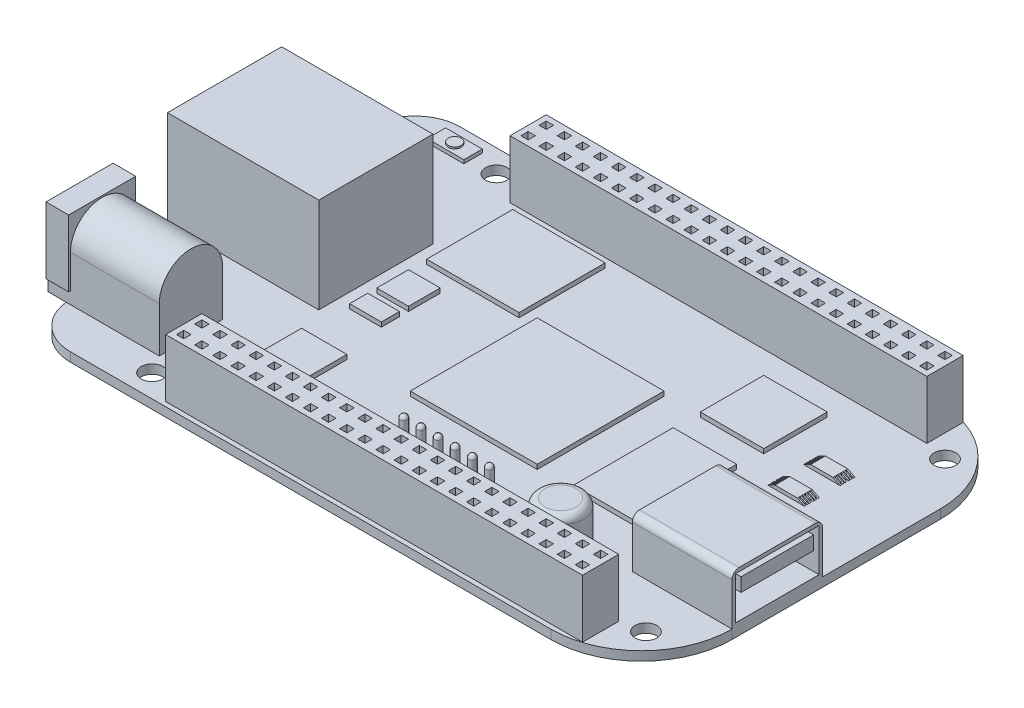
SolidWorks part; units mm, degrees
material "ABS"
ref_plane "Front Plane" through (0, 0, 0) normal (0, 0, 1) x (1, 0, 0)
ref_plane "Top Plane" through (0, 0, 0) normal (0, 1, 0) x (1, 0, 0)
ref_plane "Right Plane" through (0, 0, 0) normal (1, 0, 0) x (0, 0, -1)
sketch "Sketch1" plane through (0, 0, 0) normal (0, 1, 0) x (1, 0, 0)
  line L1 (-12.7, 0) -> (-80.01, 0)
  line L2 (0, 12.7) -> (0, 41.91)
  line L3 (-12.7, 54.61) -> (-80.01, 54.61)
  line L4 (-86.36, 6.35) -> (-86.36, 48.26)
  arc A0 (0, 12.7) -> (-12.7, 0) centre (-12.7, 12.7) cw
  arc A1 (0, 41.91) -> (-12.7, 54.61) centre (-12.7, 41.91) ccw
  arc A2 (-86.36, 6.35) -> (-80.01, 0) centre (-80.01, 6.35) ccw
  arc A3 (-86.36, 48.26) -> (-80.01, 54.61) centre (-80.01, 48.26) cw
  point P7 (0, 0)
  point P10 (0, 54.61)
  point P13 (-86.36, 0)
  dimension "D3" = 12.7
  dimension "D4" = 6.35
  dimension "D1" = 86.36
  dimension "D2" = 54.61
extrude "Boss-Extrude1" add sketch "Sketch1" along normal blind 1.27
sketch "Sketch2" plane through (0, 1.27, 0) normal (0, 1, 0) x (1, 0, 0)
  line L0 (-80.01, 0) -> (-12.7, 0) construction
  line L2 (-71.755, 51.435) -> (-71.755, 3.175) construction
  line L3 (-86.36, 48.26) -> (-86.36, 6.35) construction
  line L4 (-5.715, 48.26) -> (-5.715, 6.35) construction
  circle A0 centre (-71.755, 51.435) radius 1.524
  circle A1 centre (-71.755, 3.175) radius 1.524
  circle A2 centre (-5.715, 48.26) radius 1.524
  circle A3 centre (-5.715, 6.35) radius 1.524
  dimension "D7" = 3.048
  dimension "D1" = 48.26
  dimension "D2" = 41.91
  dimension "D3" = 6.35
  dimension "D4" = 14.605
  dimension "D5" = 80.645
  dimension "D6" = 3.175
extrude "Cut-Extrude1" cut sketch "Sketch2" along direction (0, -1, 0) on the side against the normal up to surface (1.27 mm away) up to face at (-44.4387, 0, -27.305)
sketch "Sketch3" plane through (0, 1.27, 0) normal (0, 1, 0) x (1, 0, 0)
  line L0 (-10.16, 48.895) -> (-10.16, 50.165) construction
  line L1 (-67.31, 53.975) -> (-8.89, 53.975)
  line L2 (-67.31, 53.975) -> (-67.31, 48.895)
  line L3 (-67.31, 48.895) -> (-8.89, 48.895)
  line L4 (-8.89, 53.975) -> (-8.89, 48.895)
  line L5 (-86.36, 27.305) -> (0, 27.305) construction
  line L6 (0, 12.7) -> (0, 41.91) construction
  line L7 (-66.548, 4.953) -> (-66.548, 3.937)
  line L8 (-66.548, 4.953) -> (-65.532, 4.953)
  line L9 (-10.16, 50.165) -> (-10.16, 52.705) construction
  line L10 (-10.16, 52.705) -> (-10.16, 53.975) construction
  line L11 (-13.208, 52.197) -> (-12.192, 52.197)
  line L12 (-10.668, 53.213) -> (-9.652, 53.213)
  line L13 (-10.668, 53.213) -> (-10.668, 52.197)
  line L14 (-10.668, 52.197) -> (-9.652, 52.197)
  line L15 (-9.652, 53.213) -> (-9.652, 52.197)
  line L16 (-10.668, 53.213) -> (-9.652, 52.197) construction
  line L17 (-10.668, 52.197) -> (-9.652, 53.213) construction
  line L18 (-10.668, 49.657) -> (-9.652, 49.657)
  line L19 (-10.668, 49.657) -> (-10.668, 50.673)
  line L20 (-10.668, 50.673) -> (-9.652, 50.673)
  line L21 (-9.652, 49.657) -> (-9.652, 50.673)
  line L22 (-10.668, 49.657) -> (-9.652, 50.673) construction
  line L23 (-10.668, 50.673) -> (-9.652, 49.657) construction
  line L24 (-13.208, 53.213) -> (-13.208, 52.197)
  line L25 (-13.208, 53.213) -> (-12.192, 53.213)
  line L26 (-12.192, 53.213) -> (-12.192, 52.197)
  line L27 (-13.208, 50.673) -> (-12.192, 50.673)
  line L28 (-12.192, 49.657) -> (-12.192, 50.673)
  line L29 (-13.208, 49.657) -> (-12.192, 49.657)
  line L30 (-13.208, 49.657) -> (-13.208, 50.673)
  line L31 (-15.748, 52.197) -> (-14.732, 52.197)
  line L32 (-15.748, 53.213) -> (-15.748, 52.197)
  line L33 (-15.748, 53.213) -> (-14.732, 53.213)
  line L34 (-14.732, 53.213) -> (-14.732, 52.197)
  line L35 (-15.748, 50.673) -> (-14.732, 50.673)
  line L36 (-14.732, 49.657) -> (-14.732, 50.673)
  line L37 (-15.748, 49.657) -> (-14.732, 49.657)
  line L38 (-15.748, 49.657) -> (-15.748, 50.673)
  line L39 (-18.288, 52.197) -> (-17.272, 52.197)
  line L40 (-18.288, 53.213) -> (-18.288, 52.197)
  line L41 (-18.288, 53.213) -> (-17.272, 53.213)
  line L42 (-17.272, 53.213) -> (-17.272, 52.197)
  line L43 (-18.288, 50.673) -> (-17.272, 50.673)
  line L44 (-17.272, 49.657) -> (-17.272, 50.673)
  line L45 (-18.288, 49.657) -> (-17.272, 49.657)
  line L46 (-18.288, 49.657) -> (-18.288, 50.673)
  line L47 (-20.828, 52.197) -> (-19.812, 52.197)
  line L48 (-20.828, 53.213) -> (-20.828, 52.197)
  line L49 (-20.828, 53.213) -> (-19.812, 53.213)
  line L50 (-19.812, 53.213) -> (-19.812, 52.197)
  line L51 (-20.828, 50.673) -> (-19.812, 50.673)
  line L52 (-19.812, 49.657) -> (-19.812, 50.673)
  line L53 (-20.828, 49.657) -> (-19.812, 49.657)
  line L54 (-20.828, 49.657) -> (-20.828, 50.673)
  line L55 (-23.368, 52.197) -> (-22.352, 52.197)
  line L56 (-23.368, 53.213) -> (-23.368, 52.197)
  line L57 (-23.368, 53.213) -> (-22.352, 53.213)
  line L58 (-22.352, 53.213) -> (-22.352, 52.197)
  line L59 (-23.368, 50.673) -> (-22.352, 50.673)
  line L60 (-22.352, 49.657) -> (-22.352, 50.673)
  line L61 (-23.368, 49.657) -> (-22.352, 49.657)
  line L62 (-23.368, 49.657) -> (-23.368, 50.673)
  line L63 (-25.908, 52.197) -> (-24.892, 52.197)
  line L64 (-25.908, 53.213) -> (-25.908, 52.197)
  line L65 (-25.908, 53.213) -> (-24.892, 53.213)
  line L66 (-24.892, 53.213) -> (-24.892, 52.197)
  line L67 (-25.908, 50.673) -> (-24.892, 50.673)
  line L68 (-24.892, 49.657) -> (-24.892, 50.673)
  line L69 (-25.908, 49.657) -> (-24.892, 49.657)
  line L70 (-25.908, 49.657) -> (-25.908, 50.673)
  line L71 (-28.448, 52.197) -> (-27.432, 52.197)
  line L72 (-28.448, 53.213) -> (-28.448, 52.197)
  line L73 (-28.448, 53.213) -> (-27.432, 53.213)
  line L74 (-27.432, 53.213) -> (-27.432, 52.197)
  line L75 (-28.448, 50.673) -> (-27.432, 50.673)
  line L76 (-27.432, 49.657) -> (-27.432, 50.673)
  line L77 (-28.448, 49.657) -> (-27.432, 49.657)
  line L78 (-28.448, 49.657) -> (-28.448, 50.673)
  line L79 (-30.988, 52.197) -> (-29.972, 52.197)
  line L80 (-30.988, 53.213) -> (-30.988, 52.197)
  line L81 (-30.988, 53.213) -> (-29.972, 53.213)
  line L82 (-29.972, 53.213) -> (-29.972, 52.197)
  line L83 (-30.988, 50.673) -> (-29.972, 50.673)
  line L84 (-29.972, 49.657) -> (-29.972, 50.673)
  line L85 (-30.988, 49.657) -> (-29.972, 49.657)
  line L86 (-30.988, 49.657) -> (-30.988, 50.673)
  line L87 (-33.528, 52.197) -> (-32.512, 52.197)
  line L88 (-33.528, 53.213) -> (-33.528, 52.197)
  line L89 (-33.528, 53.213) -> (-32.512, 53.213)
  line L90 (-32.512, 53.213) -> (-32.512, 52.197)
  line L91 (-33.528, 50.673) -> (-32.512, 50.673)
  line L92 (-32.512, 49.657) -> (-32.512, 50.673)
  line L93 (-33.528, 49.657) -> (-32.512, 49.657)
  line L94 (-33.528, 49.657) -> (-33.528, 50.673)
  line L95 (-36.068, 52.197) -> (-35.052, 52.197)
  line L96 (-36.068, 53.213) -> (-36.068, 52.197)
  line L97 (-36.068, 53.213) -> (-35.052, 53.213)
  line L98 (-35.052, 53.213) -> (-35.052, 52.197)
  line L99 (-36.068, 50.673) -> (-35.052, 50.673)
  line L100 (-35.052, 49.657) -> (-35.052, 50.673)
  line L101 (-36.068, 49.657) -> (-35.052, 49.657)
  line L102 (-36.068, 49.657) -> (-36.068, 50.673)
  line L103 (-38.608, 52.197) -> (-37.592, 52.197)
  line L104 (-38.608, 53.213) -> (-38.608, 52.197)
  line L105 (-38.608, 53.213) -> (-37.592, 53.213)
  line L106 (-37.592, 53.213) -> (-37.592, 52.197)
  line L107 (-38.608, 50.673) -> (-37.592, 50.673)
  line L108 (-37.592, 49.657) -> (-37.592, 50.673)
  line L109 (-38.608, 49.657) -> (-37.592, 49.657)
  line L110 (-38.608, 49.657) -> (-38.608, 50.673)
  line L111 (-41.148, 52.197) -> (-40.132, 52.197)
  line L112 (-41.148, 53.213) -> (-41.148, 52.197)
  line L113 (-41.148, 53.213) -> (-40.132, 53.213)
  line L114 (-40.132, 53.213) -> (-40.132, 52.197)
  line L115 (-41.148, 50.673) -> (-40.132, 50.673)
  line L116 (-40.132, 49.657) -> (-40.132, 50.673)
  line L117 (-41.148, 49.657) -> (-40.132, 49.657)
  line L118 (-41.148, 49.657) -> (-41.148, 50.673)
  line L119 (-43.688, 52.197) -> (-42.672, 52.197)
  line L120 (-43.688, 53.213) -> (-43.688, 52.197)
  line L121 (-43.688, 53.213) -> (-42.672, 53.213)
  line L122 (-42.672, 53.213) -> (-42.672, 52.197)
  line L123 (-43.688, 50.673) -> (-42.672, 50.673)
  line L124 (-42.672, 49.657) -> (-42.672, 50.673)
  line L125 (-43.688, 49.657) -> (-42.672, 49.657)
  line L126 (-43.688, 49.657) -> (-43.688, 50.673)
  line L127 (-46.228, 52.197) -> (-45.212, 52.197)
  line L128 (-46.228, 53.213) -> (-46.228, 52.197)
  line L129 (-46.228, 53.213) -> (-45.212, 53.213)
  line L130 (-45.212, 53.213) -> (-45.212, 52.197)
  line L131 (-46.228, 50.673) -> (-45.212, 50.673)
  line L132 (-45.212, 49.657) -> (-45.212, 50.673)
  line L133 (-46.228, 49.657) -> (-45.212, 49.657)
  line L134 (-46.228, 49.657) -> (-46.228, 50.673)
  line L135 (-48.768, 52.197) -> (-47.752, 52.197)
  line L136 (-48.768, 53.213) -> (-48.768, 52.197)
  line L137 (-48.768, 53.213) -> (-47.752, 53.213)
  line L138 (-47.752, 53.213) -> (-47.752, 52.197)
  line L139 (-48.768, 50.673) -> (-47.752, 50.673)
  line L140 (-47.752, 49.657) -> (-47.752, 50.673)
  line L141 (-48.768, 49.657) -> (-47.752, 49.657)
  line L142 (-48.768, 49.657) -> (-48.768, 50.673)
  line L143 (-51.308, 52.197) -> (-50.292, 52.197)
  line L144 (-51.308, 53.213) -> (-51.308, 52.197)
  line L145 (-51.308, 53.213) -> (-50.292, 53.213)
  line L146 (-50.292, 53.213) -> (-50.292, 52.197)
  line L147 (-51.308, 50.673) -> (-50.292, 50.673)
  line L148 (-50.292, 49.657) -> (-50.292, 50.673)
  line L149 (-51.308, 49.657) -> (-50.292, 49.657)
  line L150 (-51.308, 49.657) -> (-51.308, 50.673)
  line L151 (-53.848, 52.197) -> (-52.832, 52.197)
  line L152 (-53.848, 53.213) -> (-53.848, 52.197)
  line L153 (-53.848, 53.213) -> (-52.832, 53.213)
  line L154 (-52.832, 53.213) -> (-52.832, 52.197)
  line L155 (-53.848, 50.673) -> (-52.832, 50.673)
  line L156 (-52.832, 49.657) -> (-52.832, 50.673)
  line L157 (-53.848, 49.657) -> (-52.832, 49.657)
  line L158 (-53.848, 49.657) -> (-53.848, 50.673)
  line L159 (-56.388, 52.197) -> (-55.372, 52.197)
  line L160 (-56.388, 53.213) -> (-56.388, 52.197)
  line L161 (-56.388, 53.213) -> (-55.372, 53.213)
  line L162 (-55.372, 53.213) -> (-55.372, 52.197)
  line L163 (-56.388, 50.673) -> (-55.372, 50.673)
  line L164 (-55.372, 49.657) -> (-55.372, 50.673)
  line L165 (-56.388, 49.657) -> (-55.372, 49.657)
  line L166 (-56.388, 49.657) -> (-56.388, 50.673)
  line L167 (-58.928, 52.197) -> (-57.912, 52.197)
  line L168 (-58.928, 53.213) -> (-58.928, 52.197)
  line L169 (-58.928, 53.213) -> (-57.912, 53.213)
  line L170 (-57.912, 53.213) -> (-57.912, 52.197)
  line L171 (-58.928, 50.673) -> (-57.912, 50.673)
  line L172 (-57.912, 49.657) -> (-57.912, 50.673)
  line L173 (-58.928, 49.657) -> (-57.912, 49.657)
  line L174 (-58.928, 49.657) -> (-58.928, 50.673)
  line L175 (-61.468, 52.197) -> (-60.452, 52.197)
  line L176 (-61.468, 53.213) -> (-61.468, 52.197)
  line L177 (-61.468, 53.213) -> (-60.452, 53.213)
  line L178 (-60.452, 53.213) -> (-60.452, 52.197)
  line L179 (-61.468, 50.673) -> (-60.452, 50.673)
  line L180 (-60.452, 49.657) -> (-60.452, 50.673)
  line L181 (-61.468, 49.657) -> (-60.452, 49.657)
  line L182 (-61.468, 49.657) -> (-61.468, 50.673)
  line L183 (-64.008, 52.197) -> (-62.992, 52.197)
  line L184 (-64.008, 53.213) -> (-64.008, 52.197)
  line L185 (-64.008, 53.213) -> (-62.992, 53.213)
  line L186 (-62.992, 53.213) -> (-62.992, 52.197)
  line L187 (-64.008, 50.673) -> (-62.992, 50.673)
  line L188 (-62.992, 49.657) -> (-62.992, 50.673)
  line L189 (-64.008, 49.657) -> (-62.992, 49.657)
  line L190 (-64.008, 49.657) -> (-64.008, 50.673)
  line L191 (-66.548, 52.197) -> (-65.532, 52.197)
  line L192 (-66.548, 53.213) -> (-66.548, 52.197)
  line L193 (-66.548, 53.213) -> (-65.532, 53.213)
  line L194 (-65.532, 53.213) -> (-65.532, 52.197)
  line L195 (-66.548, 50.673) -> (-65.532, 50.673)
  line L196 (-65.532, 49.657) -> (-65.532, 50.673)
  line L197 (-66.548, 49.657) -> (-65.532, 49.657)
  line L198 (-66.548, 49.657) -> (-66.548, 50.673)
  line L199 (-66.548, 49.657) -> (-65.532, 50.673) construction
  line L200 (-86.36, 48.26) -> (-86.36, 6.35) construction
  line L201 (-65.532, 4.953) -> (-65.532, 3.937)
  line L202 (-12.7, 54.61) -> (-80.01, 54.61) construction
  line L203 (-66.548, 3.937) -> (-65.532, 3.937)
  line L204 (-65.532, 1.397) -> (-65.532, 2.413)
  line L205 (-66.548, 1.397) -> (-65.532, 1.397)
  line L206 (-66.548, 1.397) -> (-66.548, 2.413)
  line L207 (-66.548, 2.413) -> (-65.532, 2.413)
  line L208 (-64.008, 4.953) -> (-64.008, 3.937)
  line L209 (-64.008, 4.953) -> (-62.992, 4.953)
  line L210 (-62.992, 4.953) -> (-62.992, 3.937)
  line L211 (-64.008, 3.937) -> (-62.992, 3.937)
  line L212 (-62.992, 1.397) -> (-62.992, 2.413)
  line L213 (-64.008, 1.397) -> (-62.992, 1.397)
  line L214 (-64.008, 1.397) -> (-64.008, 2.413)
  line L215 (-64.008, 2.413) -> (-62.992, 2.413)
  line L216 (-61.468, 4.953) -> (-61.468, 3.937)
  line L217 (-61.468, 4.953) -> (-60.452, 4.953)
  line L218 (-60.452, 4.953) -> (-60.452, 3.937)
  line L219 (-61.468, 3.937) -> (-60.452, 3.937)
  line L220 (-60.452, 1.397) -> (-60.452, 2.413)
  line L221 (-61.468, 1.397) -> (-60.452, 1.397)
  line L222 (-61.468, 1.397) -> (-61.468, 2.413)
  line L223 (-61.468, 2.413) -> (-60.452, 2.413)
  line L224 (-58.928, 4.953) -> (-58.928, 3.937)
  line L225 (-58.928, 4.953) -> (-57.912, 4.953)
  line L226 (-57.912, 4.953) -> (-57.912, 3.937)
  line L227 (-58.928, 3.937) -> (-57.912, 3.937)
  line L228 (-57.912, 1.397) -> (-57.912, 2.413)
  line L229 (-58.928, 1.397) -> (-57.912, 1.397)
  line L230 (-58.928, 1.397) -> (-58.928, 2.413)
  line L231 (-58.928, 2.413) -> (-57.912, 2.413)
  line L232 (-56.388, 4.953) -> (-56.388, 3.937)
  line L233 (-56.388, 4.953) -> (-55.372, 4.953)
  line L234 (-55.372, 4.953) -> (-55.372, 3.937)
  line L235 (-56.388, 3.937) -> (-55.372, 3.937)
  line L236 (-55.372, 1.397) -> (-55.372, 2.413)
  line L237 (-56.388, 1.397) -> (-55.372, 1.397)
  line L238 (-56.388, 1.397) -> (-56.388, 2.413)
  line L239 (-56.388, 2.413) -> (-55.372, 2.413)
  line L240 (-53.848, 4.953) -> (-53.848, 3.937)
  line L241 (-53.848, 4.953) -> (-52.832, 4.953)
  line L242 (-52.832, 4.953) -> (-52.832, 3.937)
  line L243 (-53.848, 3.937) -> (-52.832, 3.937)
  line L244 (-52.832, 1.397) -> (-52.832, 2.413)
  line L245 (-53.848, 1.397) -> (-52.832, 1.397)
  line L246 (-53.848, 1.397) -> (-53.848, 2.413)
  line L247 (-53.848, 2.413) -> (-52.832, 2.413)
  line L248 (-51.308, 4.953) -> (-51.308, 3.937)
  line L249 (-51.308, 4.953) -> (-50.292, 4.953)
  line L250 (-50.292, 4.953) -> (-50.292, 3.937)
  line L251 (-51.308, 3.937) -> (-50.292, 3.937)
  line L252 (-50.292, 1.397) -> (-50.292, 2.413)
  line L253 (-51.308, 1.397) -> (-50.292, 1.397)
  line L254 (-51.308, 1.397) -> (-51.308, 2.413)
  line L255 (-51.308, 2.413) -> (-50.292, 2.413)
  line L256 (-48.768, 4.953) -> (-48.768, 3.937)
  line L257 (-48.768, 4.953) -> (-47.752, 4.953)
  line L258 (-47.752, 4.953) -> (-47.752, 3.937)
  line L259 (-48.768, 3.937) -> (-47.752, 3.937)
  line L260 (-47.752, 1.397) -> (-47.752, 2.413)
  line L261 (-48.768, 1.397) -> (-47.752, 1.397)
  line L262 (-48.768, 1.397) -> (-48.768, 2.413)
  line L263 (-48.768, 2.413) -> (-47.752, 2.413)
  line L264 (-46.228, 4.953) -> (-46.228, 3.937)
  line L265 (-46.228, 4.953) -> (-45.212, 4.953)
  line L266 (-45.212, 4.953) -> (-45.212, 3.937)
  line L267 (-46.228, 3.937) -> (-45.212, 3.937)
  line L268 (-45.212, 1.397) -> (-45.212, 2.413)
  line L269 (-46.228, 1.397) -> (-45.212, 1.397)
  line L270 (-46.228, 1.397) -> (-46.228, 2.413)
  line L271 (-46.228, 2.413) -> (-45.212, 2.413)
  line L272 (-43.688, 4.953) -> (-43.688, 3.937)
  line L273 (-43.688, 4.953) -> (-42.672, 4.953)
  line L274 (-42.672, 4.953) -> (-42.672, 3.937)
  line L275 (-43.688, 3.937) -> (-42.672, 3.937)
  line L276 (-42.672, 1.397) -> (-42.672, 2.413)
  line L277 (-43.688, 1.397) -> (-42.672, 1.397)
  line L278 (-43.688, 1.397) -> (-43.688, 2.413)
  line L279 (-43.688, 2.413) -> (-42.672, 2.413)
  line L280 (-41.148, 4.953) -> (-41.148, 3.937)
  line L281 (-41.148, 4.953) -> (-40.132, 4.953)
  line L282 (-40.132, 4.953) -> (-40.132, 3.937)
  line L283 (-41.148, 3.937) -> (-40.132, 3.937)
  line L284 (-40.132, 1.397) -> (-40.132, 2.413)
  line L285 (-41.148, 1.397) -> (-40.132, 1.397)
  line L286 (-41.148, 1.397) -> (-41.148, 2.413)
  line L287 (-41.148, 2.413) -> (-40.132, 2.413)
  line L288 (-38.608, 4.953) -> (-38.608, 3.937)
  line L289 (-38.608, 4.953) -> (-37.592, 4.953)
  line L290 (-37.592, 4.953) -> (-37.592, 3.937)
  line L291 (-38.608, 3.937) -> (-37.592, 3.937)
  line L292 (-37.592, 1.397) -> (-37.592, 2.413)
  line L293 (-38.608, 1.397) -> (-37.592, 1.397)
  line L294 (-38.608, 1.397) -> (-38.608, 2.413)
  line L295 (-38.608, 2.413) -> (-37.592, 2.413)
  line L296 (-36.068, 4.953) -> (-36.068, 3.937)
  line L297 (-36.068, 4.953) -> (-35.052, 4.953)
  line L298 (-35.052, 4.953) -> (-35.052, 3.937)
  line L299 (-36.068, 3.937) -> (-35.052, 3.937)
  line L300 (-35.052, 1.397) -> (-35.052, 2.413)
  line L301 (-36.068, 1.397) -> (-35.052, 1.397)
  line L302 (-36.068, 1.397) -> (-36.068, 2.413)
  line L303 (-36.068, 2.413) -> (-35.052, 2.413)
  line L304 (-33.528, 4.953) -> (-33.528, 3.937)
  line L305 (-33.528, 4.953) -> (-32.512, 4.953)
  line L306 (-32.512, 4.953) -> (-32.512, 3.937)
  line L307 (-33.528, 3.937) -> (-32.512, 3.937)
  line L308 (-32.512, 1.397) -> (-32.512, 2.413)
  line L309 (-33.528, 1.397) -> (-32.512, 1.397)
  line L310 (-33.528, 1.397) -> (-33.528, 2.413)
  line L311 (-33.528, 2.413) -> (-32.512, 2.413)
  line L312 (-30.988, 4.953) -> (-30.988, 3.937)
  line L313 (-30.988, 4.953) -> (-29.972, 4.953)
  line L314 (-29.972, 4.953) -> (-29.972, 3.937)
  line L315 (-30.988, 3.937) -> (-29.972, 3.937)
  line L316 (-29.972, 1.397) -> (-29.972, 2.413)
  line L317 (-30.988, 1.397) -> (-29.972, 1.397)
  line L318 (-30.988, 1.397) -> (-30.988, 2.413)
  line L319 (-30.988, 2.413) -> (-29.972, 2.413)
  line L320 (-28.448, 4.953) -> (-28.448, 3.937)
  line L321 (-28.448, 4.953) -> (-27.432, 4.953)
  line L322 (-27.432, 4.953) -> (-27.432, 3.937)
  line L323 (-28.448, 3.937) -> (-27.432, 3.937)
  line L324 (-27.432, 1.397) -> (-27.432, 2.413)
  line L325 (-28.448, 1.397) -> (-27.432, 1.397)
  line L326 (-28.448, 1.397) -> (-28.448, 2.413)
  line L327 (-28.448, 2.413) -> (-27.432, 2.413)
  line L328 (-25.908, 4.953) -> (-25.908, 3.937)
  line L329 (-25.908, 4.953) -> (-24.892, 4.953)
  line L330 (-24.892, 4.953) -> (-24.892, 3.937)
  line L331 (-25.908, 3.937) -> (-24.892, 3.937)
  line L332 (-24.892, 1.397) -> (-24.892, 2.413)
  line L333 (-25.908, 1.397) -> (-24.892, 1.397)
  line L334 (-25.908, 1.397) -> (-25.908, 2.413)
  line L335 (-25.908, 2.413) -> (-24.892, 2.413)
  line L336 (-23.368, 4.953) -> (-23.368, 3.937)
  line L337 (-23.368, 4.953) -> (-22.352, 4.953)
  line L338 (-22.352, 4.953) -> (-22.352, 3.937)
  line L339 (-23.368, 3.937) -> (-22.352, 3.937)
  line L340 (-22.352, 1.397) -> (-22.352, 2.413)
  line L341 (-23.368, 1.397) -> (-22.352, 1.397)
  line L342 (-23.368, 1.397) -> (-23.368, 2.413)
  line L343 (-23.368, 2.413) -> (-22.352, 2.413)
  line L344 (-20.828, 4.953) -> (-20.828, 3.937)
  line L345 (-20.828, 4.953) -> (-19.812, 4.953)
  line L346 (-19.812, 4.953) -> (-19.812, 3.937)
  line L347 (-20.828, 3.937) -> (-19.812, 3.937)
  line L348 (-19.812, 1.397) -> (-19.812, 2.413)
  line L349 (-20.828, 1.397) -> (-19.812, 1.397)
  line L350 (-20.828, 1.397) -> (-20.828, 2.413)
  line L351 (-20.828, 2.413) -> (-19.812, 2.413)
  line L352 (-18.288, 4.953) -> (-18.288, 3.937)
  line L353 (-18.288, 4.953) -> (-17.272, 4.953)
  line L354 (-17.272, 4.953) -> (-17.272, 3.937)
  line L355 (-18.288, 3.937) -> (-17.272, 3.937)
  line L356 (-17.272, 1.397) -> (-17.272, 2.413)
  line L357 (-18.288, 1.397) -> (-17.272, 1.397)
  line L358 (-18.288, 1.397) -> (-18.288, 2.413)
  line L359 (-18.288, 2.413) -> (-17.272, 2.413)
  line L360 (-15.748, 4.953) -> (-15.748, 3.937)
  line L361 (-15.748, 4.953) -> (-14.732, 4.953)
  line L362 (-14.732, 4.953) -> (-14.732, 3.937)
  line L363 (-15.748, 3.937) -> (-14.732, 3.937)
  line L364 (-14.732, 1.397) -> (-14.732, 2.413)
  line L365 (-15.748, 1.397) -> (-14.732, 1.397)
  line L366 (-15.748, 1.397) -> (-15.748, 2.413)
  line L367 (-15.748, 2.413) -> (-14.732, 2.413)
  line L368 (-13.208, 4.953) -> (-13.208, 3.937)
  line L369 (-13.208, 4.953) -> (-12.192, 4.953)
  line L370 (-12.192, 4.953) -> (-12.192, 3.937)
  line L371 (-13.208, 3.937) -> (-12.192, 3.937)
  line L372 (-12.192, 1.397) -> (-12.192, 2.413)
  line L373 (-13.208, 1.397) -> (-12.192, 1.397)
  line L374 (-13.208, 1.397) -> (-13.208, 2.413)
  line L375 (-9.652, 4.953) -> (-9.652, 3.937)
  line L376 (-10.668, 3.937) -> (-9.652, 3.937)
  line L377 (-10.668, 4.953) -> (-10.668, 3.937)
  line L378 (-10.668, 4.953) -> (-9.652, 4.953)
  line L379 (-9.652, 1.397) -> (-9.652, 2.413)
  line L380 (-10.668, 2.413) -> (-9.652, 2.413)
  line L381 (-10.668, 1.397) -> (-10.668, 2.413)
  line L382 (-10.668, 1.397) -> (-9.652, 1.397)
  line L383 (-13.208, 2.413) -> (-12.192, 2.413)
  line L384 (-8.89, 0.635) -> (-8.89, 5.715)
  line L385 (-67.31, 5.715) -> (-8.89, 5.715)
  line L386 (-67.31, 0.635) -> (-67.31, 5.715)
  line L387 (-67.31, 0.635) -> (-8.89, 0.635)
  circle A0 centre (-66.04, 50.165) radius 0.1361
  dimension "D1" = 1.016
  dimension "D2" = 2.54
  dimension "D3" = 5.08
  dimension "D4" = 58.42
  dimension "D5" = 1.27
  dimension "D7" = 20.32
  dimension "D8" = 0.635
  dimension "D6" = 23
extrude "Boss-Extrude2" add sketch "Sketch3" along normal blind 8.128 contours L4 L1 L2 L3 L193 L194 L191 L192 L185 L186 L183 L184 L177 L178 L175 L176 L169 L170 L167 L168 L161 L162 L159 L160 L153 L154 L151 L152 L145 L146 L143 L144 L137 L138 L135 L136 L129 L130 L127 L128 L121 | L386 L387 L384 L385 L374 L383 L372 L373 L382 L381 L380 L379 L366 L367 L364 L365 L363 L360 L361 L362 L350 L351 L348 L349 L347 L344 L345 L346 L334 L335 L332 L333 L331 L328 L329 L330 L318 L319 L316 L317 L315 region at (-38.1, 1.27, -51.435) region at (-38.1, 1.27, -3.175)
sketch "Sketch4" plane through (0, 1.27, 0) normal (0, 1, 0) x (1, 0, 0)
  line L0 (-86.36, 48.26) -> (-86.36, 6.35) construction
  line L1 (-67.691, 22.479) -> (-88.9, 22.479)
  line L2 (-67.691, 22.479) -> (-67.691, 38.481)
  line L3 (-67.691, 38.481) -> (-88.9, 38.481)
  line L4 (-88.9, 22.479) -> (-88.9, 38.481)
  line L5 (-12.7, 54.61) -> (-80.01, 54.61) construction
  dimension "D1" = 2.54
  dimension "D2" = 21.209
  dimension "D3" = 16.002
  dimension "D4" = 16.129
extrude "Boss-Extrude3" add sketch "Sketch4" along normal blind 13.335
sketch "Sketch5" plane through (-88.9, 0, 0) normal (-1, 0, 0) x (0, 0, 1)
  line L0 (-30.48, 2.286) -> (-30.48, 3.937) construction
  line L1 (-36.83, 12.065) -> (-24.13, 12.065)
  line L2 (-36.83, 12.065) -> (-36.83, 5.461)
  line L3 (-36.83, 5.461) -> (-24.13, 5.461)
  line L4 (-24.13, 12.065) -> (-24.13, 5.461)
  line L5 (-33.655, 5.461) -> (-27.305, 5.461)
  line L6 (-33.655, 5.461) -> (-33.655, 3.937)
  line L7 (-33.655, 3.937) -> (-27.305, 3.937)
  line L8 (-27.305, 5.461) -> (-27.305, 3.937)
  line L9 (-32.512, 3.937) -> (-28.448, 3.937)
  line L10 (-32.512, 3.937) -> (-32.512, 2.286)
  line L11 (-32.512, 2.286) -> (-28.448, 2.286)
  line L12 (-28.448, 3.937) -> (-28.448, 2.286)
  line L13 (-30.48, 3.937) -> (-30.48, 5.461) construction
  line L14 (-38.481, 14.605) -> (-22.479, 14.605) construction
  line L15 (-36.83, 12.065) -> (-38.481, 12.065) construction
  line L16 (-38.481, 14.605) -> (-38.481, 1.27) construction
  line L17 (-24.13, 12.065) -> (-22.479, 12.065) construction
  line L18 (-22.479, 14.605) -> (-22.479, 1.27) construction
  dimension "D1" = 12.7
  dimension "D2" = 6.604
  dimension "D3" = 2.54
  dimension "D4" = 1.524
  dimension "D5" = 1.651
  dimension "D6" = 4.064
  dimension "D7" = 6.35
extrude "Cut-Extrude2" cut sketch "Sketch5" against normal blind 17.78 contours L4 L1 L2 L3 | L8 L3 L6 L7 | L12 L7 L10 L11 region at (-88.9, 8.763, -30.48) region at (-88.9, 4.699, -30.48) region at (-88.9, 3.1115, -30.48)
sketch "Sketch6" plane through (0, 1.27, 0) normal (0, 1, 0) x (1, 0, 0)
  line L0 (-67.31, 48.895) -> (-8.89, 48.895) construction
  line L1 (-65.659, 35.56) -> (-52.705, 35.56)
  line L2 (-65.659, 35.56) -> (-65.659, 47.625)
  line L3 (-65.659, 47.625) -> (-52.705, 47.625)
  line L4 (-52.705, 35.56) -> (-52.705, 47.625)
  line L5 (-50.8, 36.195) -> (-33.02, 36.195)
  line L6 (-50.8, 36.195) -> (-50.8, 18.415)
  line L7 (-50.8, 18.415) -> (-33.02, 18.415)
  line L8 (-33.02, 36.195) -> (-33.02, 18.415)
  line L9 (-27.94, 45.085) -> (-19.05, 45.085)
  line L10 (-27.94, 45.085) -> (-27.94, 36.195)
  line L11 (-27.94, 36.195) -> (-19.05, 36.195)
  line L12 (-19.05, 45.085) -> (-19.05, 36.195)
  line L13 (-27.94, 32.385) -> (-19.05, 32.385)
  line L14 (-27.94, 32.385) -> (-27.94, 18.415)
  line L15 (-27.94, 18.415) -> (-19.05, 18.415)
  line L16 (-19.05, 32.385) -> (-19.05, 18.415)
  line L17 (-66.04, 18.415) -> (-59.69, 18.415)
  line L18 (-66.04, 18.415) -> (-66.04, 12.065)
  line L19 (-66.04, 12.065) -> (-59.69, 12.065)
  line L20 (-59.69, 18.415) -> (-59.69, 12.065)
  line L21 (-65.659, 27.305) -> (-61.214, 27.305)
  line L22 (-65.659, 27.305) -> (-65.659, 24.765)
  line L23 (-65.659, 24.765) -> (-61.214, 24.765)
  line L24 (-61.214, 27.305) -> (-61.214, 24.765)
  line L25 (-65.659, 33.02) -> (-61.214, 33.02)
  line L26 (-65.659, 33.02) -> (-65.659, 28.575)
  line L27 (-65.659, 28.575) -> (-61.214, 28.575)
  line L28 (-61.214, 33.02) -> (-61.214, 28.575)
  line L29 (0, 12.7) -> (0, 41.91) construction
  line L30 (-67.31, 48.895) -> (-8.89, 48.895) construction
  line L31 (-67.31, 5.715) -> (-8.89, 5.715) construction
  line L33 (-67.31, 0.635) -> (-67.31, 5.715) construction
  dimension "D1" = 8.89
  dimension "D2" = 13.97
  dimension "D3" = 3.81
  dimension "D4" = 3.81
  dimension "D5" = 19.05
  dimension "D6" = 17.78
  dimension "D7" = 12.7
  dimension "D8" = 33.02
  dimension "D9" = 12.954
  dimension "D10" = 12.065
  dimension "D11" = 1.905
  dimension "D12" = 4.445
  dimension "D13" = 2.54
  dimension "D14" = 1.27
  dimension "D15" = 2.54
  dimension "D16" = 1.27
  dimension "D17" = 6.35
  dimension "D18" = 6.35
  dimension "D19" = 1.27
extrude "Boss-Extrude4" add sketch "Sketch6" along normal blind 0.635
sketch "Sketch7" plane through (0, 1.27, 0) normal (0, 1, 0) x (1, 0, 0)
  line L1 (0, 12.7) -> (-13.97, 12.7)
  line L2 (0, 12.7) -> (0, 25.4)
  line L3 (0, 25.4) -> (-13.97, 25.4)
  line L4 (-13.97, 12.7) -> (-13.97, 25.4)
  line L5 (-80.01, 0) -> (-12.7, 0) construction
  line L6 (0, 12.7) -> (0, 41.91) construction
  dimension "D1" = 12.7
  dimension "D2" = 13.97
  dimension "D3" = 25.4
extrude "Boss-Extrude5" add sketch "Sketch7" along normal blind 6.985
sketch "Sketch8" plane through (0, 0, 0) normal (1, 0, 0) x (0, 0, -1)
  line L0 (12.7, 8.255) -> (25.4, 8.255) construction
  line L1 (13.97, 6.985) -> (24.13, 6.985)
  line L2 (13.97, 6.985) -> (13.97, 5.08)
  line L3 (13.97, 5.08) -> (24.13, 5.08)
  line L4 (24.13, 6.985) -> (24.13, 5.08)
  line L5 (13.208, 7.747) -> (24.892, 7.747)
  line L6 (13.208, 7.747) -> (13.208, 1.778)
  line L7 (13.208, 1.778) -> (24.892, 1.778)
  line L8 (24.892, 7.747) -> (24.892, 1.778)
  line L9 (25.4, 8.255) -> (25.4, 1.27) construction
  line L10 (12.7, 8.255) -> (12.7, 1.27) construction
  line L11 (12.7, 1.27) -> (0, 1.27) construction
  line L12 (13.97, 7.18) -> (13.208, 7.18) construction
  line L14 (24.892, 6.9479) -> (24.13, 6.9479) construction
  dimension "D1" = 0.508
  dimension "D2" = 0.508
  dimension "D3" = 0.508
  dimension "D4" = 0.508
  dimension "D5" = 1.905
  dimension "D6" = 10.16
  dimension "D7" = 3.175
extrude "Cut-Extrude3" cut sketch "Sketch8" against normal blind 12.7
sketch "Sketch9" plane through (0, 1.27, 0) normal (0, 1, 0) x (1, 0, 0)
  line L0 (-88.9, 38.481) -> (-88.9, 22.479) construction
  line L1 (-73.279, 5.715) -> (-88.9, 5.715)
  line L2 (-73.279, 5.715) -> (-73.279, 14.605)
  line L3 (-73.279, 14.605) -> (-88.9, 14.605)
  line L4 (-88.9, 5.715) -> (-88.9, 14.605)
  line L5 (-67.31, 5.715) -> (-8.89, 5.715) construction
  circle A0 centre (-71.755, 3.175) radius 1.524 construction
  dimension "D1" = 8.89
extrude "Boss-Extrude6" add sketch "Sketch9" along normal blind 6.35
sketch "Sketch10" plane through (-88.9, 0, 0) normal (-1, 0, 0) x (0, 0, 1)
  line L0 (-14.605, 7.62) -> (-5.715, 7.62) construction
  circle A0 centre (-10.16, 7.62) radius 4.445
  circle A1 centre (-10.16, 7.62) radius 3.4925
  circle A2 centre (-10.16, 7.62) radius 0.635
  line M3 (-5.715, 7.62) -> (-14.605, 7.62)
  dimension "D1" = 1.27
  dimension "D2" = 6.985
extrude "Boss-Extrude7" add sketch "Sketch10" along direction (1, 0, 0) on the side against the normal up to surface (15.621 mm away) contours A1 A0 M3 | A1 A0 M3 | A2 M3 | A2 A1 M3 region at (-88.9, 7.7194, -6.1912) region at (-88.9, 3.2744, -10.16) region at (-88.9, 9.1437, -10.16) region at (-88.9, 7.8895, -10.16) up to face at (-73.279, 4.445, -10.16)
sketch "Sketch11" plane through (-88.9, 0, 0) normal (-1, 0, 0) x (0, 0, 1)
  line L0 (-14.605, 7.62) -> (-14.605, 1.27) construction
  line L1 (-5.461, 2.952) -> (-14.859, 2.952)
  line L2 (-5.461, 2.952) -> (-5.461, 12.288)
  line L3 (-5.461, 12.288) -> (-14.859, 12.288)
  line L4 (-14.859, 2.952) -> (-14.859, 12.288)
  line L5 (-5.461, 2.952) -> (-14.859, 12.288) construction
  line L6 (-5.461, 12.288) -> (-14.859, 2.952) construction
  point P0 (-10.16, 7.62)
  dimension "D1" = 0.254
extrude "Boss-Extrude8" add sketch "Sketch11" against normal blind 3.175
extrude "Cut-Extrude4" cut sketch "Sketch10<3>" against normal blind 12.7 contours A2 A1 M3 | A2 A1 M3 region at (-88.9, 9.1437, -10.16) region at (-88.9, 6.0963, -10.16)
sketch "Sketch10<3>" plane through (-88.9, 0, 0) normal (-1, 0, 0) x (0, 0, 1) same geometry as "Sketch10"
fillet "Fillet1" radius 0.635 1 edges at (-88.9, 7.62, -9.525)
sketch "Sketch13" plane through (0, 1.27, 0) normal (0, 1, 0) x (1, 0, 0)
  line L0 (-85.1081, 45.625) -> (-85.1081, 44.3766)
  line L1 (-80.4022, 50.3766) -> (-80.4022, 52.967)
  line L2 (-80.4022, 40.3766) -> (-75.2569, 40.3766)
  line L3 (-80.4022, 40.3766) -> (-80.4022, 42.967)
  line L4 (-80.4022, 42.967) -> (-75.2569, 42.967)
  line L5 (-85.1081, 47.625) -> (-81.6152, 47.625)
  line L6 (-85.1081, 47.625) -> (-85.1081, 46.3766)
  line L7 (-85.1081, 46.3766) -> (-81.6152, 46.3766)
  line L8 (-81.6152, 47.625) -> (-81.6152, 46.3766)
  line L9 (-85.1081, 45.625) -> (-81.6152, 45.625)
  line L10 (-81.6152, 45.625) -> (-81.6152, 44.3766)
  line L11 (-85.1081, 44.3766) -> (-81.6152, 44.3766)
  line L12 (-85.1081, 43.625) -> (-85.1081, 42.3766)
  line L13 (-85.1081, 43.625) -> (-81.6152, 43.625)
  line L14 (-81.6152, 43.625) -> (-81.6152, 42.3766)
  line L15 (-85.1081, 42.3766) -> (-81.6152, 42.3766)
  line L16 (-85.1081, 41.625) -> (-85.1081, 40.3766)
  line L17 (-85.1081, 41.625) -> (-81.6152, 41.625)
  line L18 (-81.6152, 41.625) -> (-81.6152, 40.3766)
  line L19 (-85.1081, 40.3766) -> (-81.6152, 40.3766)
  line L20 (-75.2569, 40.3766) -> (-75.2569, 42.967)
  line L21 (-80.4022, 50.3766) -> (-75.2569, 50.3766)
  line L22 (-75.2569, 50.3766) -> (-75.2569, 52.967)
  line L23 (-80.4022, 52.967) -> (-75.2569, 52.967)
  line L24 (-9.8278, 38.5983) -> (-9.8278, 38.3983)
  line L25 (-9.8278, 34.5526) -> (-9.8278, 34.7526)
  line L26 (-10.8276, 33.5983) -> (-9.8278, 33.5983)
  line L27 (-10.8276, 33.5983) -> (-10.8276, 33.3983)
  line L28 (-10.8276, 33.3983) -> (-9.8278, 33.3983)
  line L29 (-13.97, 34.7526) -> (-10.8276, 34.7526)
  line L30 (-13.97, 34.7526) -> (-13.97, 32.6861)
  line L31 (-13.97, 32.6861) -> (-10.8276, 32.6861)
  line L32 (-10.8276, 34.7526) -> (-10.8276, 32.6861)
  line L33 (-10.8276, 39.1779) -> (-9.8278, 39.1779)
  line L34 (-10.8276, 38.8404) -> (-9.8278, 38.8404)
  line L35 (-13.97, 38.3983) -> (-14.9698, 38.3983)
  line L36 (-10.8276, 39.7526) -> (-10.8276, 37.6861)
  line L37 (-9.8278, 33.5983) -> (-9.8278, 33.3983)
  line L38 (-10.8276, 33.2607) -> (-9.8278, 33.2607)
  line L39 (-10.8276, 33.2607) -> (-10.8276, 33.0607)
  line L40 (-10.8276, 33.0607) -> (-9.8278, 33.0607)
  line L41 (-9.8278, 33.2607) -> (-9.8278, 33.0607)
  line L42 (-10.8276, 32.8861) -> (-9.8278, 32.8861)
  line L43 (-10.8276, 32.8861) -> (-10.8276, 32.6861)
  line L44 (-10.8276, 32.6861) -> (-9.8278, 32.6861)
  line L45 (-9.8278, 32.8861) -> (-9.8278, 32.6861)
  line L46 (-10.8276, 34.7526) -> (-9.8278, 34.7526)
  line L47 (-10.8276, 34.5526) -> (-10.8276, 34.7526)
  line L48 (-10.8276, 34.5526) -> (-9.8278, 34.5526)
  line L49 (-9.8278, 34.1779) -> (-9.8278, 34.3779)
  line L50 (-10.8276, 34.3779) -> (-9.8278, 34.3779)
  line L51 (-10.8276, 34.1779) -> (-10.8276, 34.3779)
  line L52 (-10.8276, 34.1779) -> (-9.8278, 34.1779)
  line L53 (-9.8278, 33.8404) -> (-9.8278, 34.0404)
  line L54 (-10.8276, 34.0404) -> (-9.8278, 34.0404)
  line L55 (-10.8276, 33.8404) -> (-10.8276, 34.0404)
  line L56 (-10.8276, 33.8404) -> (-9.8278, 33.8404)
  line L57 (-10.8276, 39.5526) -> (-9.8278, 39.5526)
  line L58 (-13.97, 33.8404) -> (-14.9698, 33.8404)
  line L59 (-13.97, 33.8404) -> (-13.97, 34.0404)
  line L60 (-13.97, 34.0404) -> (-14.9698, 34.0404)
  line L61 (-14.9698, 33.8404) -> (-14.9698, 34.0404)
  line L62 (-13.97, 34.1779) -> (-14.9698, 34.1779)
  line L63 (-13.97, 34.1779) -> (-13.97, 34.3779)
  line L64 (-13.97, 34.3779) -> (-14.9698, 34.3779)
  line L65 (-14.9698, 34.1779) -> (-14.9698, 34.3779)
  line L66 (-13.97, 34.5526) -> (-14.9698, 34.5526)
  line L67 (-13.97, 34.5526) -> (-13.97, 34.7526)
  line L68 (-13.97, 34.7526) -> (-14.9698, 34.7526)
  line L69 (-14.9698, 32.8861) -> (-14.9698, 32.6861)
  line L70 (-13.97, 32.6861) -> (-14.9698, 32.6861)
  line L71 (-13.97, 32.8861) -> (-13.97, 32.6861)
  line L72 (-13.97, 32.8861) -> (-14.9698, 32.8861)
  line L73 (-14.9698, 33.2607) -> (-14.9698, 33.0607)
  line L74 (-13.97, 33.0607) -> (-14.9698, 33.0607)
  line L75 (-13.97, 33.2607) -> (-13.97, 33.0607)
  line L76 (-13.97, 33.2607) -> (-14.9698, 33.2607)
  line L77 (-14.9698, 33.5983) -> (-14.9698, 33.3983)
  line L78 (-13.97, 34.7526) -> (-13.97, 32.6861)
  line L79 (-13.97, 33.3983) -> (-14.9698, 33.3983)
  line L80 (-13.97, 33.5983) -> (-13.97, 33.3983)
  line L81 (-13.97, 33.5983) -> (-14.9698, 33.5983)
  line L82 (-14.9698, 34.5526) -> (-14.9698, 34.7526)
  line L83 (-13.97, 39.3779) -> (-14.9698, 39.3779)
  line L84 (-14.9698, 37.8861) -> (-14.9698, 37.6861)
  line L85 (-10.8276, 37.8861) -> (-9.8278, 37.8861)
  line L86 (-10.8276, 39.1779) -> (-10.8276, 39.3779)
  line L87 (-13.97, 38.2607) -> (-14.9698, 38.2607)
  line L88 (-14.9698, 38.8404) -> (-14.9698, 39.0404)
  line L89 (-14.9698, 39.5526) -> (-14.9698, 39.7526)
  line L90 (-9.8278, 37.8861) -> (-9.8278, 37.6861)
  line L91 (-13.97, 39.7526) -> (-14.9698, 39.7526)
  line L92 (-14.9698, 38.2607) -> (-14.9698, 38.0607)
  line L93 (-10.8276, 38.3983) -> (-9.8278, 38.3983)
  line L94 (-13.97, 38.8404) -> (-14.9698, 38.8404)
  line L95 (-13.97, 38.5983) -> (-13.97, 38.3983)
  line L96 (-10.8276, 38.5983) -> (-10.8276, 38.3983)
  line L97 (-14.9698, 39.1779) -> (-14.9698, 39.3779)
  line L98 (-13.97, 37.6861) -> (-14.9698, 37.6861)
  line L99 (-13.97, 39.7526) -> (-10.8276, 39.7526)
  line L100 (-10.8276, 38.2607) -> (-10.8276, 38.0607)
  line L101 (-9.8278, 38.2607) -> (-9.8278, 38.0607)
  line L102 (-14.9698, 38.5983) -> (-14.9698, 38.3983)
  line L103 (-9.8278, 39.5526) -> (-9.8278, 39.7526)
  line L104 (-13.97, 39.1779) -> (-14.9698, 39.1779)
  line L105 (-13.97, 37.6861) -> (-10.8276, 37.6861)
  line L106 (-10.8276, 39.7526) -> (-9.8278, 39.7526)
  line L107 (-13.97, 38.0607) -> (-14.9698, 38.0607)
  line L108 (-9.8278, 38.8404) -> (-9.8278, 39.0404)
  line L109 (-13.97, 38.8404) -> (-13.97, 39.0404)
  line L110 (-13.97, 38.5983) -> (-14.9698, 38.5983)
  line L111 (-13.97, 39.7526) -> (-13.97, 37.6861)
  line L112 (-10.8276, 39.5526) -> (-10.8276, 39.7526)
  line L113 (-13.97, 39.5526) -> (-14.9698, 39.5526)
  line L114 (-13.97, 37.8861) -> (-13.97, 37.6861)
  line L115 (-10.8276, 38.2607) -> (-9.8278, 38.2607)
  line L116 (-10.8276, 38.0607) -> (-9.8278, 38.0607)
  line L117 (-10.8276, 39.3779) -> (-9.8278, 39.3779)
  line L118 (-10.8276, 38.8404) -> (-10.8276, 39.0404)
  line L119 (-13.97, 39.7526) -> (-13.97, 37.6861)
  line L120 (-10.8276, 38.5983) -> (-9.8278, 38.5983)
  line L121 (-13.97, 39.1779) -> (-13.97, 39.3779)
  line L122 (-10.8276, 37.8861) -> (-10.8276, 37.6861)
  line L123 (-9.8278, 39.1779) -> (-9.8278, 39.3779)
  line L124 (-10.8276, 39.0404) -> (-9.8278, 39.0404)
  line L125 (-13.97, 38.2607) -> (-13.97, 38.0607)
  line L126 (-13.97, 39.0404) -> (-14.9698, 39.0404)
  line L127 (-10.8276, 37.6861) -> (-9.8278, 37.6861)
  line L128 (-13.97, 39.5526) -> (-13.97, 39.7526)
  line L129 (-13.97, 37.8861) -> (-14.9698, 37.8861)
  dimension "D1" = 4
  dimension "D2" = 2
extrude "Boss-Extrude9" add sketch "Sketch13" along normal blind 0.5 contours L23 L1 L21 L22 | L16 L19 L18 L17 | L12 L15 L14 L13 | L0 L11 L10 L9 | L8 L5 L6 L7 | L2 L20 L4 L3 | L99 L111 L109 L95 L105 L36 | L113 L111 L91 L89 | L95 L110 L102 L35 | L111 L129 L84 L98 | L36 L127 L90 L85 | L120 L36 L93 L24 | L33 L123 L117 L36 | L106 L36 L57 L103 | L30 L72 L69 L70 | L30 L76 L73 L74 | L32 L29 L30 L78 L31 L27 | L45 L42 L32 L44 | L41 L38 L32 L40 | L37 L26 L27 L28 | L32 L56 L53 L54 | L32 L52 L49 L50 | L32 L48 L25 L46 | L4 L20 L2 L3 | L9 L10 L11 L0 | L7 L8 L5 L6 | L83 L97 L104 L121 | L126 L88 L94 L109 | L87 L92 L107 L125 | L116 L101 L115 L100 | L124 L108 L34 L118 | L79 L77 L81 L80 | L60 L61 L58 L59 | L62 L65 L64 L63 | L67 L66 L82 L68 region at (-83.3617, 1.27, -45.0008) region at (-77.8296, 1.27, -51.6718) region at (-77.8296, 1.27, -41.6718) region at (-83.3617, 1.27, -47.0008) region at (-83.3617, 1.27, -43.0008) region at (-83.3617, 1.27, -41.0008) region at (-10.3277, 1.27, -38.4983) region at (-12.3988, 1.27, -38.7193) region at (-10.3277, 1.27, -39.2779) region at (-10.3277, 1.27, -37.7861) region at (-10.3277, 1.27, -39.6526) region at (-14.4699, 1.27, -37.7861) region at (-14.4699, 1.27, -39.6526) region at (-14.4699, 1.27, -38.4983) region at (-10.3277, 1.27, -34.6526) region at (-12.3988, 1.27, -33.7193) region at (-10.3277, 1.27, -34.2779) region at (-10.3277, 1.27, -33.9404) region at (-10.3277, 1.27, -33.4983) region at (-10.3277, 1.27, -33.1607) region at (-10.3277, 1.27, -32.7861) region at (-14.4699, 1.27, -33.1607) region at (-14.4699, 1.27, -32.7861)
chamfer "Chamfer1" distance 0.5 distance2 1 2 edges at (-14.9698, 1.77, -39.6526) (-9.8278, 1.77, -39.6526) first distance on face at (-14.9698, 1.52, -39.6526) first distance on face at (-9.8278, 1.52, -39.6526)
chamfer "Chamfer2" distance 0.5 distance2 1 2 edges at (-9.8278, 1.77, -32.7861) (-14.9698, 1.77, -32.7861) first distance on face at (-9.8278, 1.52, -32.7861) first distance on face at (-14.9698, 1.52, -32.7861)
sketch "Sketch14" plane through (0, 1.77, 0) normal (0, 1, 0) x (1, 0, 0)
  line L0 (-84.3639, 45.2638) -> (-84.3639, 44.8063)
  line L1 (-84.3639, 47.2638) -> (-82.305, 47.2638)
  line L2 (-84.3639, 47.2638) -> (-84.3639, 46.8063)
  line L3 (-84.3639, 46.8063) -> (-82.305, 46.8063)
  line L4 (-82.305, 47.2638) -> (-82.305, 46.8063)
  line L5 (-84.3639, 45.2638) -> (-82.305, 45.2638)
  line L6 (-82.305, 45.2638) -> (-82.305, 44.8063)
  line L7 (-84.3639, 44.8063) -> (-82.305, 44.8063)
  line L8 (-84.3639, 43.2638) -> (-84.3639, 42.8063)
  line L9 (-84.3639, 43.2638) -> (-82.305, 43.2638)
  line L10 (-82.305, 43.2638) -> (-82.305, 42.8063)
  line L11 (-84.3639, 42.8063) -> (-82.305, 42.8063)
  line L12 (-84.3639, 41.2638) -> (-84.3639, 40.8063)
  line L13 (-84.3639, 41.2638) -> (-82.305, 41.2638)
  line L14 (-82.305, 41.2638) -> (-82.305, 40.8063)
  line L15 (-84.3639, 40.8063) -> (-82.305, 40.8063)
  circle A0 centre (-77.8296, 51.6718) radius 0.9
  circle A1 centre (-77.8296, 41.6718) radius 0.9
  dimension "D1" = 4
extrude "Boss-Extrude10" add sketch "Sketch14" along normal blind 0.25
fillet "Fillet2" radius 1 2 edges at (-6.985, 8.255, -12.7) (-6.985, 8.255, -25.4)
sketch "Sketch15" plane through (0, 1.27, 0) normal (0, 1, 0) x (1, 0, 0)
  line L1 (-27.5112, 6.4431) -> (-41.5112, 6.4431)
  line L2 (-27.5112, 6.4431) -> (-27.5112, 8.2431)
  line L3 (-27.5112, 8.2431) -> (-41.5112, 8.2431)
  line L4 (-41.5112, 6.4431) -> (-41.5112, 8.2431)
extrude "Boss-Extrude11" add sketch "Sketch15" along normal blind 1
sketch "Sketch16" plane through (0, 2.27, 0) normal (0, 1, 0) x (1, 0, 0)
  circle A0 centre (-40.64, 7.3431) radius 0.5
  circle A1 centre (-38.24, 7.3431) radius 0.5
  circle A2 centre (-35.84, 7.3431) radius 0.5
  circle A3 centre (-33.44, 7.3431) radius 0.5
  circle A4 centre (-31.04, 7.3431) radius 0.5
  circle A5 centre (-28.64, 7.3431) radius 0.5
  dimension "D1" = 6
extrude "Boss-Extrude12" add sketch "Sketch16" along normal blind 7.5
fillet "Fillet3" radius 0.5 6 edges at (-40.64, 9.77, -6.8431) (-38.24, 9.77, -6.8431) (-35.84, 9.77, -6.8431) (-33.44, 9.77, -6.8431) (-31.04, 9.77, -6.8431) (-28.64, 9.77, -6.8431)
sketch "Sketch17" plane through (0, 1.27, 0) normal (0, 1, 0) x (1, 0, 0)
  circle A0 centre (-21.7424, 10.4145) radius 3.2
extrude "Boss-Extrude13" add sketch "Sketch17" along normal blind 6.2
fillet "Fillet4" radius 1 1 edges at (-21.7424, 7.47, -7.2145)
ref_plane "Plane1" through (-43.18, 0, 0) normal (1, 0, 0) x (0, 0, -1)
